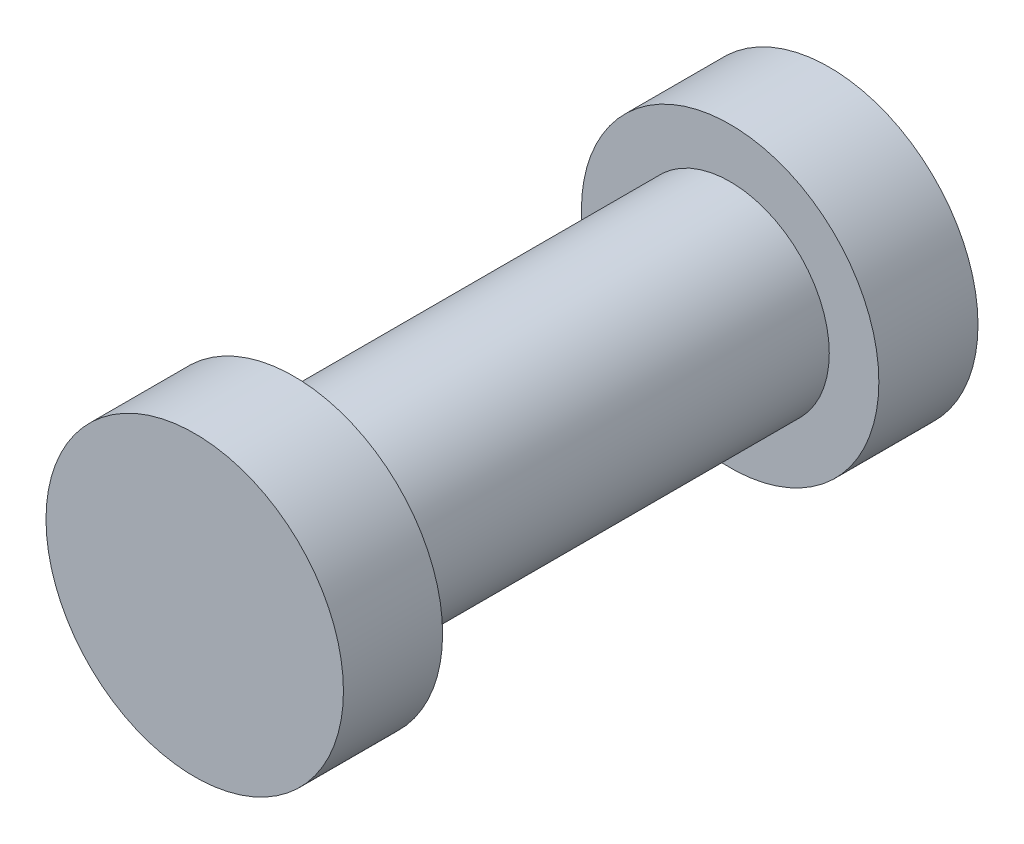
SolidWorks part; units mm, degrees
ref_plane "Front Plane" through (0, 0, 0) normal (0, 0, 1) x (1, 0, 0)
ref_plane "Top Plane" through (0, 0, 0) normal (0, 1, 0) x (1, 0, 0)
ref_plane "Right Plane" through (0, 0, 0) normal (1, 0, 0) x (0, 0, -1)
sketch "Sketch1" plane through (0, 0, 0) normal (0, 0, 1) x (1, 0, 0)
  circle A0 centre (0, 0) radius 5
  circle A1 centre (0, 0) radius 7.5
  dimension "D1" = 10
  dimension "D2" = 15
extrude "Boss-Extrude1" add sketch "Sketch1" along normal blind 32 contours A0 | A1 A0 region at (0, 0, 0) region at (-7.2879, 0, 0)
extrude "Cut-Extrude1" cut sketch "Sketch1<6>" along normal offset from surface (22 mm away) 5 from offset 5 contours A1 A0 region at (-7.2879, 0, 0) up to face at (7.5, 0, 32)
sketch "Sketch1<6>" plane through (0, 0, 0) normal (0, 0, 1) x (1, 0, 0) same geometry as "Sketch1"
